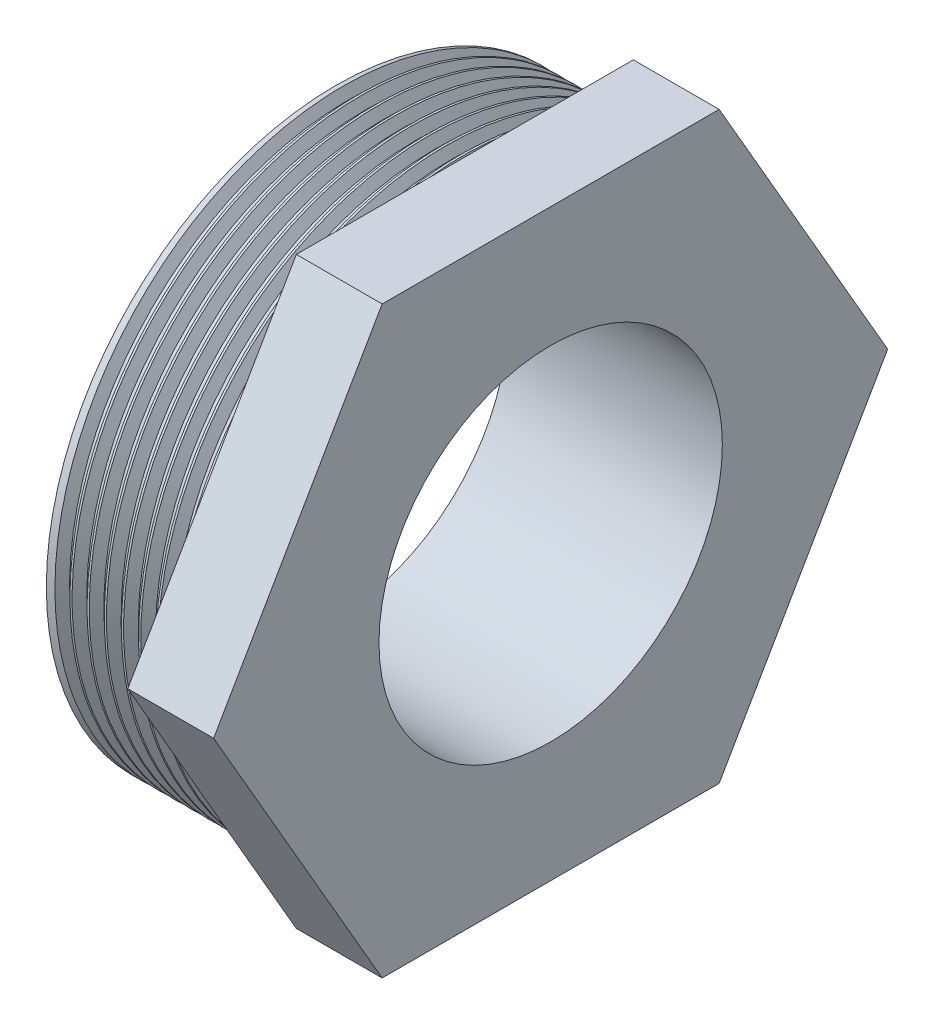
SolidWorks part; units mm, degrees
ref_plane "Front Plane" through (0, 0, 0) normal (0, 0, 1) x (1, 0, 0)
ref_plane "Top Plane" through (0, 0, 0) normal (0, 1, 0) x (1, 0, 0)
ref_plane "Right Plane" through (0, 0, 0) normal (1, 0, 0) x (0, 0, -1)
sketch "Sketch1" plane through (0, 0, 0) normal (1, 0, 0) x (0, 0, -1)
  line L0 (39.2598, 0) -> (0, 0) construction
  line L1 (39.2598, 0) -> (19.6299, 34)
  line L2 (19.6299, 34) -> (-19.6299, 34)
  line L3 (-19.6299, 34) -> (-39.2598, 0)
  line L4 (-39.2598, 0) -> (-19.6299, -34)
  line L5 (-19.6299, -34) -> (19.6299, -34)
  line L6 (19.6299, -34) -> (39.2598, 0)
  circle A0 centre (0, 0) radius 34 construction
  circle A1 centre (0, 0) radius 20
  dimension "D1" = 40
  dimension "D2" = 68
extrude "Boss-Extrude1" add sketch "Sketch1" along normal blind 10
sketch "Sketch2" plane through (0, 0, 0) normal (-1, 0, 0) x (0, 0, 1)
  circle A0 centre (0, 0) radius 20
  circle A1 centre (0, 0) radius 33.75
  circle A2 centre (0, 0) radius 20 construction
  dimension "D1" = 67.5
extrude "Boss-Extrude2" add sketch "Sketch2" along normal blind 15
thread "Thread1" pitch 2 method cut profile "Thread Profile4" start angle 0, offset 0, length 0, pitch 2, diameter 67.5
ref_plane "Plane4" through (-15, 0, -33.75) normal (0, -1, 0) x (0, 0, -1)
sketch "Thread Profile4" plane through (-15, 0, -33.75) normal (0, -1, 0) x (0, 0, -1)
  line L0 (0, 0) -> (0, 2) construction
  line L11 (0, 0) -> (0, 1.75)
  line L12 (0, 1.75) -> (-1.0825, 1.125)
  line L13 (-1.0825, 1.125) -> (-1.0825, 0.625)
  line L15 (-1.0825, 0.625) -> (0, 0)
  line L17 (-1.0825, 0.875) -> (0, 0.875) construction
  point P2 (0, 0)
  dimension "Pitch" = 2
  dimension "Profile_Angle" = 60
  dimension "Profile_Land" = 0.5
  dimension "Profile_Height" = 1.0825
